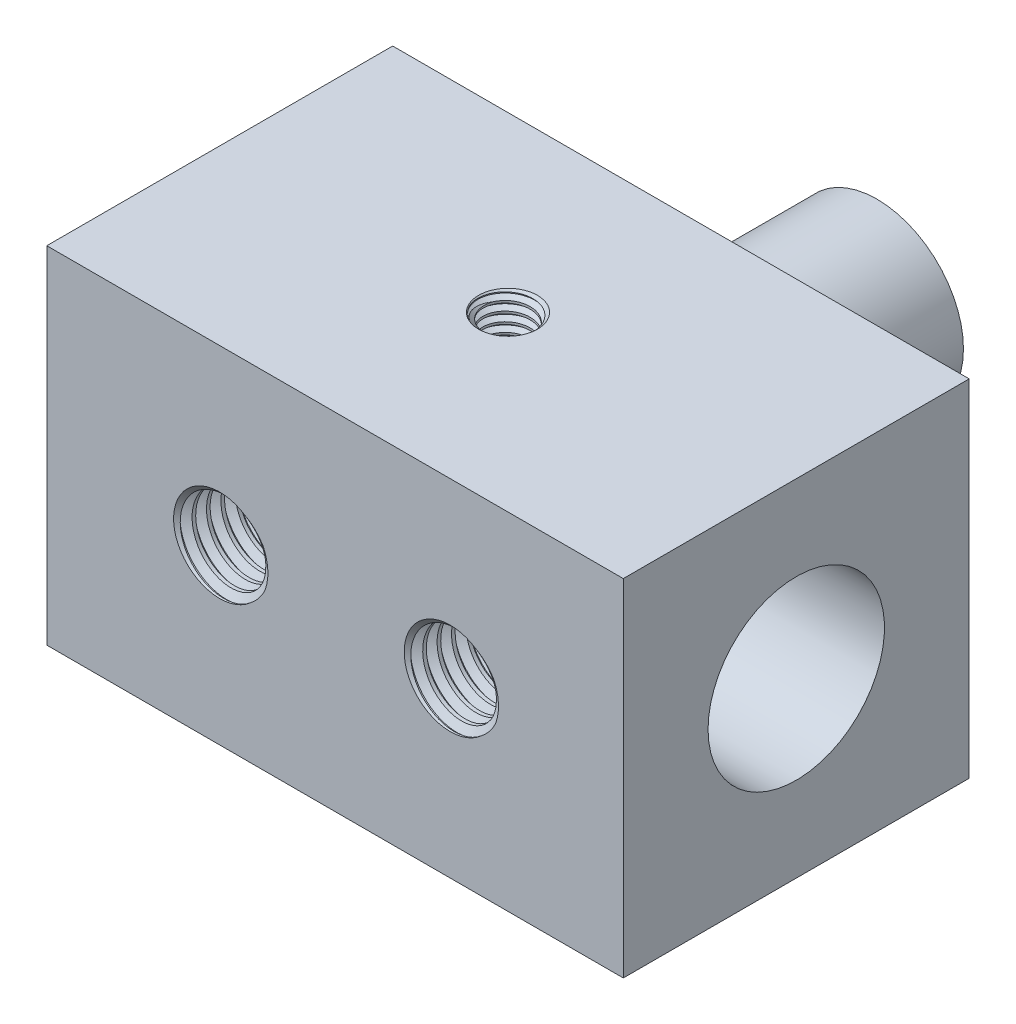
SolidWorks part; units mm, degrees
ref_plane "Front Plane" through (0, 0, 0) normal (0, 0, 1) x (1, 0, 0)
ref_plane "Top Plane" through (0, 0, 0) normal (0, 1, 0) x (1, 0, 0)
ref_plane "Right Plane" through (0, 0, 0) normal (1, 0, 0) x (0, 0, -1)
sketch "Sketch1" plane through (0, 0, 0) normal (0, 0, 1) x (1, 0, 0)
  circle A2 centre (0, 0) radius 7.5
  dimension "D1" = 15
extrude "Boss-Extrude1" add sketch "Sketch1" along normal blind 17
sketch "Sketch3" plane through (0, 0, 17) normal (0, 0, 1) x (1, 0, 0)
  line L1 (-25, -15) -> (25, -15)
  line L2 (-25, -15) -> (-25, 15)
  line L3 (-25, 15) -> (25, 15)
  line L4 (25, -15) -> (25, 15)
  line L5 (-25, -15) -> (25, 15) construction
  line L6 (-25, 15) -> (25, -15) construction
  point P0 (0, 0)
extrude "Boss-Extrude2" add sketch "Sketch3" along normal blind 30
sketch "Sketch4" plane through (-25, 0, 0) normal (-1, 0, 0) x (0, 0, 1)
  line L0 (17, 15) -> (47, -15) construction
  line L1 (47, -15) -> (47, 15) construction
  line L2 (47, 15) -> (17, -15) construction
  circle A0 centre (32, 0) radius 7.65
  point P4 (32, 0)
  dimension "D1" = 15.3
extrude "Cut-Extrude1" cut sketch "Sketch4" against normal blind 76
fillet "Fillet1" radius 2 1 edges at (7.5, 0, 17)
sketch "Sketch5" plane through (0, 0, 47) normal (0, 0, 1) x (1, 0, 0)
  line L0 (-25, 15) -> (25, -15) construction
  line L1 (25, 15) -> (-25, -15) construction
  line L2 (-25, 0) -> (25, 0) construction
  line L3 (-25, 15) -> (-25, -15) construction
  line L4 (25, -15) -> (25, 15) construction
  circle A1 centre (-10, 0) radius 3.5
  circle A2 centre (10, 0) radius 3.5
  dimension "D1" = 20
  dimension "D3" = 7
  dimension "D4" = 7
  dimension "D2" = 10
extrude "Cut-Extrude2" cut sketch "Sketch5" against normal blind 10
sketch "Sketch6" plane through (0, -15, 0) normal (0, -1, 0) x (1, 0, 0)
  line L0 (-25, 47) -> (25, 17) construction
  line L1 (-25, 17) -> (25, 47) construction
  circle A0 centre (0, 32) radius 2.05
  dimension "D1" = 4.1
extrude "Cut-Extrude3" cut sketch "Sketch6" against normal blind 46
chamfer "Chamfer1" distance 0.5 angle 45 4 edges at (0, -15, 29.95) (-6.5, 0, 47) (13.5, 0, 47) (0, 15, 29.95)
sketch "Sketch7" plane through (-25, 0, 0) normal (-1, 0, 0) x (0, 0, 1)
  line L0 (17, 0) -> (45.0802, 0) construction
  line L1 (17, 15) -> (17, -15) construction
  line L2 (32, 15) -> (32, -21.0644) construction
  line L3 (47, 15) -> (17, 15) construction
  line L4 (32, 15) -> (32, 21.2675) construction
thread "Thread1" pitch 1.25 method cut profile "Thread Profile1" start angle 0, offset 3, length 15, pitch 1.25, diameter 7
ref_plane "Plane1" through (6.5, 0, 48.0802) normal (0, -1, 0) x (-1, 0, 0)
sketch "Thread Profile1" plane through (6.5, 0, 48.0802) normal (0, -1, 0) x (-1, 0, 0)
  line L0 (0, 0) -> (0, 1.25) construction
  line L1 (0, 0) -> (0.6766, 0.3906)
  line L2 (0.6766, 0.3906) -> (0.6766, 0.5469)
  line L3 (0.6766, 0.5469) -> (0, 0.9375)
  line L4 (0.6766, 0.4687) -> (0, 0.4687) construction
  line L11 (0, 0) -> (0, 0.9375)
  point P2 (0, 0)
  dimension "Pitch" = 1.25
  dimension "Profile_Angle" = 60
  dimension "Profile_Land" = 0.1562
  dimension "Profile_Height" = 0.6766
thread "Thread2" pitch 1.25 method cut profile "Thread Profile2" start angle 0, offset 3, length 15, pitch 1.25, diameter 7
ref_plane "Plane2" through (-13.5, 0, 48.0802) normal (0, -1, 0) x (-1, 0, 0)
sketch "Thread Profile2" plane through (-13.5, 0, 48.0802) normal (0, -1, 0) x (-1, 0, 0)
  line L0 (0, 0) -> (0, 1.25) construction
  line L1 (0, 0) -> (0.6766, 0.3906)
  line L2 (0.6766, 0.3906) -> (0.6766, 0.5469)
  line L3 (0.6766, 0.5469) -> (0, 0.9375)
  line L4 (0.6766, 0.4687) -> (0, 0.4687) construction
  line L11 (0, 0) -> (0, 0.9375)
  point P2 (0, 0)
  dimension "Pitch" = 1.25
  dimension "Profile_Angle" = 60
  dimension "Profile_Land" = 0.1562
  dimension "Profile_Height" = 0.6766
thread "Thread3" pitch 0.8 method cut profile "Thread Profile3" start angle 0, offset 0, length 40, pitch 0.8, diameter 4.1
ref_plane "Plane3" through (2.05, -21.0644, 32) normal (0, 0, 1) x (1, 0, 0)
sketch "Thread Profile3" plane through (2.05, -21.0644, 32) normal (0, 0, 1) x (1, 0, 0)
  line L0 (0, 0) -> (0, 0.8) construction
  line L1 (0, 0) -> (0.433, 0.25)
  line L2 (0.433, 0.25) -> (0.433, 0.35)
  line L3 (0.433, 0.35) -> (0, 0.6)
  line L4 (0.433, 0.3) -> (0, 0.3) construction
  line L11 (0, 0) -> (0, 0.6)
  point P2 (0, 0)
  dimension "Pitch" = 0.8
  dimension "Profile_Angle" = 60
  dimension "Profile_Land" = 0.1
  dimension "Profile_Height" = 0.433
